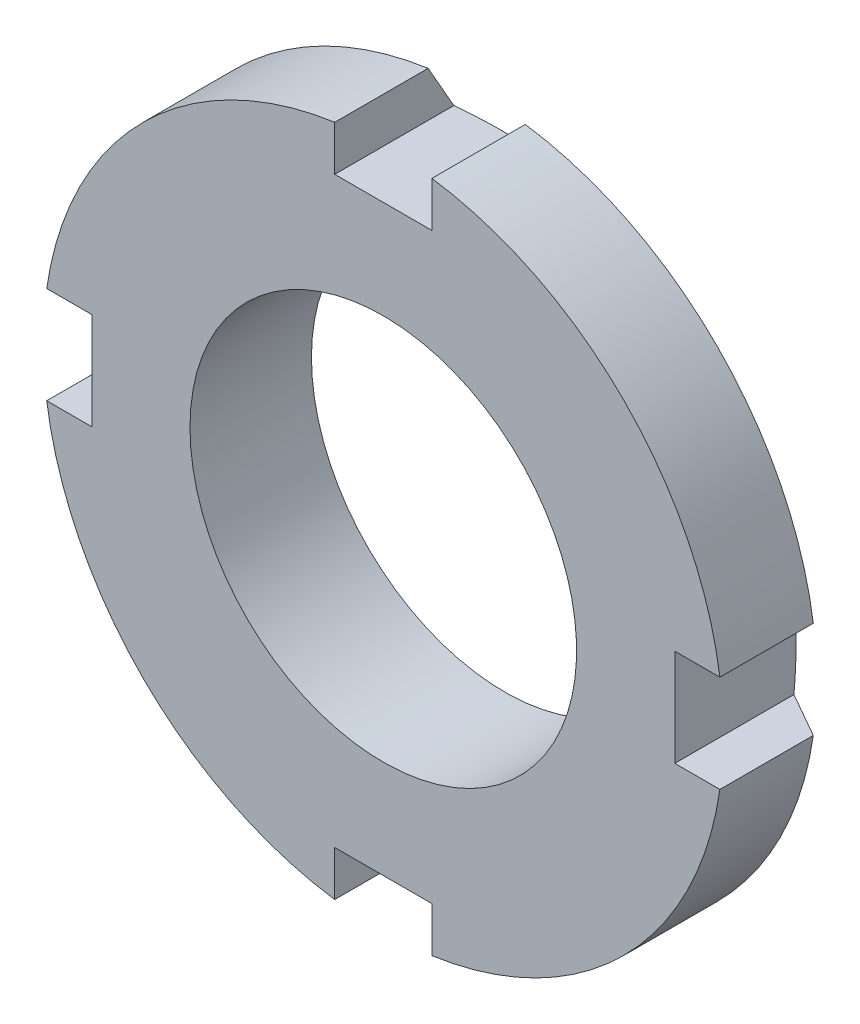
SolidWorks part; units mm, degrees
material "Handl."
ref_plane "Płaszczyzna przednia" through (0, 0, 0) normal (0, 0, 1) x (1, 0, 0)
ref_plane "Płaszczyzna górna" through (0, 0, 0) normal (0, 1, 0) x (1, 0, 0)
ref_plane "Płaszczyzna prawa" through (0, 0, 0) normal (1, 0, 0) x (0, 0, -1)
sketch "Szkic1" plane through (0, 0, 0) normal (1, 0, 0) x (0, 0, -1)
  line L0 (0, 0) -> (5, 0) construction
  line L1 (0, 0) -> (0, 14)
  line L2 (0, 14) -> (3.8453, 14)
  line L3 (3.8453, 14) -> (5, 12)
  line L4 (5, 12) -> (5, 0)
  line L5 (5, 0) -> (0, 0)
  dimension "D1" = 28
  dimension "D2" = 30
  dimension "D3" = 24
  dimension "D4" = 5
revolve "Obrót1" add sketch "Szkic1" angle 360 about L0
sketch "Szkic2" plane through (0, 0, -5) normal (0, 0, -1) x (-1, 0, 0)
  circle A0 centre (0, 0) radius 7.9585
  dimension "D1" = 15.917
extrude "Wytnij-wyciągnięcie1" cut sketch "Szkic2" against normal up to next
cosmetic thread "Oznaczenie gwintu1" parameters "D2"=17
sketch "Szkic3" plane through (0, 0, 0) normal (0, 0, 1) x (1, 0, 0)
  line L1 (-2, 14) -> (2, 14)
  line L2 (-2, 14) -> (-2, 12)
  line L3 (-2, 12) -> (2, 12)
  line L4 (2, 14) -> (2, 12)
  circle A0 centre (0, 0) radius 14 construction
  point P6 (0, 12)
  dimension "D1" = 4
  dimension "D2" = 2
extrude "Wytnij-wyciągnięcie2" cut sketch "Szkic3" against normal up to next
pattern_circular "Szyk kołowy1" count 4 over 360 about axis through (0, 0, 0) along (0, 0, 1) of "Wytnij-wyciągnięcie2"
